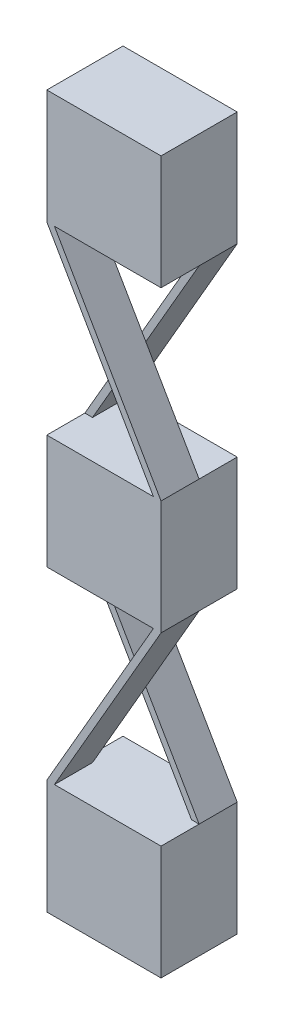
SolidWorks part; units mm, degrees
material "PET"
ref_plane "Front Plane" through (0, 0, 0) normal (0, 0, 1) x (1, 0, 0)
ref_plane "Top Plane" through (0, 0, 0) normal (0, 1, 0) x (1, 0, 0)
ref_plane "Right Plane" through (0, 0, 0) normal (1, 0, 0) x (0, 0, -1)
sketch "Sketch1" plane through (0, 0, 0) normal (0, 0, 1) x (1, 0, 0)
  line L0 (0, 0) -> (57.9688, 0) construction
  line L1 (7.5, 12.1244) -> (-7.5, 12.1244)
  line L2 (7.5, -27.1244) -> (-7.5, -27.1244)
  line L3 (7.5, -27.1244) -> (7.5, -12.1244)
  line L4 (7.5, -12.1244) -> (-7.5, -12.1244)
  line L5 (-7.5, -27.1244) -> (-7.5, -12.1244)
  line L6 (7.5, -27.1244) -> (-7.5, -12.1244) construction
  line L7 (7.5, -12.1244) -> (-7.5, -27.1244) construction
  line L8 (-7.5, 27.1244) -> (-7.5, 12.1244)
  line L9 (0, 0) -> (0, 41.5625) construction
  line L10 (7.5, 27.1244) -> (-7.5, 27.1244)
  line L11 (7.5, 27.1244) -> (7.5, 12.1244)
  line L12 (-7.5, 12.1244) -> (6.5, -12.1244)
  line L13 (6.5, -12.1244) -> (7.5, -12.1244)
  line L14 (7.5, -12.1244) -> (-6.5, 12.1244)
  line L15 (-6.5, 12.1244) -> (-7.5, 12.1244)
  line L16 (7.5, 12.1244) -> (-6.5, -12.1244)
  line L17 (-7.5, -12.1244) -> (6.5, 12.1244)
  point P1 (0, -19.6244)
  dimension "D1" = 15
  dimension "D2" = 60
  dimension "D3" = 1
extrude "Boss-Extrude1" add sketch "Sketch1" along normal mid plane 10 contours L5 L2 L3 L4 region at (0, -19.6244, 0)
extrude "Boss-Extrude2" add sketch "Sketch1<3>" against normal blind 5 from surface contours L17 L4 L16 L12 | L17 L14 L16 L1 | L17 L12 L16 L14 region at (3.6296, 6.276, 0) region at (0, 0, 0) region at (-3.6296, -6.276, 0) starting at face at (0, -19.6244, 5)
sketch "Sketch1<3>" plane through (0, 0, 0) normal (0, 0, 1) x (1, 0, 0) same geometry as "Sketch1"
extrude "Boss-Extrude3" add sketch "Sketch1<4>" along normal blind 5 from surface contours L12 L17 L14 L1 | L14 L16 L12 L4 | L17 L12 L16 L14 region at (0, 0, 0) region at (3.6296, -6.276, 0) region at (-3.6296, 6.276, 0) starting at face at (0, -19.6244, -5)
sketch "Sketch1<4>" plane through (0, 0, 0) normal (0, 0, 1) x (1, 0, 0) same geometry as "Sketch1"
extrude "Boss-Extrude4" add sketch "Sketch1<5>" along normal mid plane 10 contours L11 L10 L8 L1 region at (0, 19.6244, 0)
sketch "Sketch1<5>" plane through (0, 0, 0) normal (0, 0, 1) x (1, 0, 0) same geometry as "Sketch1"
ref_plane "Plane1" through (0, 19.6244, 0) normal (0, -1, 0) x (-1, 0, 0)
mirror "Mirror2" about plane through (0, 19.6244, 0) normal (0, -1, 0) of "Boss-Extrude2", "Boss-Extrude3"
mirror "Mirror3" about plane through (0, 19.6244, 0) normal (0, -1, 0) of "Boss-Extrude1"
equation "\"a\"= 5"
equation "\"D1@Boss-Extrude2\"=\"a\""
equation "\"D1@Boss-Extrude3\"= \"a\""
